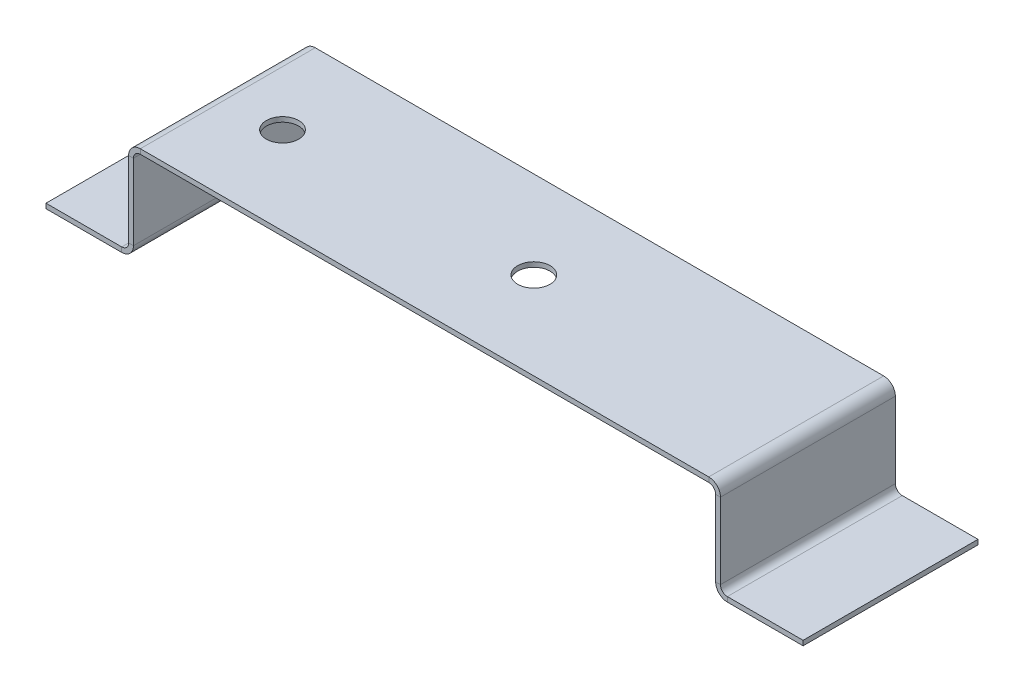
SolidWorks part; units mm, degrees
note: The reader was unsure of these and kept them because the rebuilt part matched: flange length of "Edge-Flange1", "Edge-Flange2", "Edge-Flange3", "Edge-Flange4".
ref_plane "Front Plane" through (0, 0, 0) normal (0, 0, 1) x (1, 0, 0)
ref_plane "Top Plane" through (0, 0, 0) normal (0, 1, 0) x (1, 0, 0)
ref_plane "Right Plane" through (0, 0, 0) normal (1, 0, 0) x (0, 0, -1)
sketch "Sketch1" plane through (0, 0, 0) normal (0, 1, 0) x (1, 0, 0)
  line L1 (-41.275, -12.7) -> (41.275, -12.7)
  line L2 (-41.275, -12.7) -> (-41.275, 12.7)
  line L3 (-41.275, 12.7) -> (41.275, 12.7)
  line L4 (41.275, -12.7) -> (41.275, 12.7)
  line L5 (-41.275, -12.7) -> (41.275, 12.7) construction
  line L6 (-41.275, 12.7) -> (41.275, -12.7) construction
  point P0 (0, 0)
  dimension "D1" = 25.4
  dimension "D2" = 82.55
base flange "Base-Flange1" sketch "Sketch1" thickness 0.7 reverse thickness direction no parameters "D1"=1
edge flange "Edge-Flange1" sketch "Sketch8" flange angle 90 flange length 12.7 flange position bend outside bend radius 1 thickness 0.7 relief rectangular parameters "D6"=0
sketch "Sketch8" plane through (41.275, -0.7, 0) normal (-1, 0, 0) x (0, 0, -1)
  line L2 (-12.7, 0) -> (-12.7, 12)
  line L3 (-12.7, 12) -> (12.7, 12)
  line L4 (12.7, 12) -> (12.7, 0)
  line L6 (12.7, 0) -> (-12.7, 0) construction
  line L7 (12.7, 0) -> (-12.7, 0)
bend "EdgeBend1" bend radius 1 bend angle 90 parameters "D5"=1
edge flange "Edge-Flange2" sketch "Sketch11" flange angle 90 flange length 12.7 flange position bend outside bend radius 1 thickness 0.7 relief rectangular parameters "D6"=0
sketch "Sketch11" plane through (42.975, -12.7, 0) normal (0, -1, 0) x (0, 0, -1)
  line L0 (12.7, 0) -> (-12.7, 0) construction
  line L1 (12.7, 0) -> (-12.7, 0)
  line L2 (-12.7, 0) -> (-12.7, 12)
  line L3 (-12.7, 12) -> (12.7, 12)
  line L4 (12.7, 12) -> (12.7, 0)
bend "EdgeBend2" bend radius 1 bend angle 90 parameters "D5"=2
edge flange "Edge-Flange3" sketch "Sketch15" flange angle 90 flange length 12.7 flange position bend outside bend radius 1 thickness 0.7 relief rectangular parameters "D6"=0
sketch "Sketch15" plane through (-41.275, -0.7, 0) normal (1, 0, 0) x (0, 0, 1)
  line L1 (12.7, 0) -> (-12.7, 0) construction
  line L2 (-12.7, 0) -> (-12.7, 12)
  line L3 (-12.7, 12) -> (12.7, 12)
  line L4 (12.7, 12) -> (12.7, 0)
  line L5 (12.7, 0) -> (-12.7, 0)
bend "EdgeBend3" bend radius 1 bend angle 90 parameters "D5"=3
edge flange "Edge-Flange4" sketch "Sketch18" flange angle 90 flange length 12.7 flange position bend outside bend radius 1 thickness 0.7 relief rectangular parameters "D6"=0
sketch "Sketch18" plane through (-42.975, -12.7, 0) normal (0, 1, 0) x (0, 0, -1)
  line L1 (12.7, 0) -> (-12.7, 0) construction
  line L2 (-12.7, 0) -> (-12.7, 12)
  line L3 (-12.7, 12) -> (12.7, 12)
  line L4 (12.7, 12) -> (12.7, 0)
  line L5 (12.7, 0) -> (-12.7, 0)
bend "EdgeBend4" bend radius 1 bend angle 90 parameters "D5"=4
sketch "Sketch19" plane through (0, 0, 0) normal (0, 1, 0) x (1, 0, 0)
  line L0 (41.275, 12.7) -> (-41.275, 12.7) construction
  line L1 (-41.275, 12.7) -> (-41.275, -12.7) construction
  line L2 (41.275, -12.7) -> (41.275, 12.7) construction
  circle A0 centre (-33.3248, 0) radius 2.35
  circle A1 centre (3.175, 0) radius 2.35
  dimension "D1" = 12.7
  dimension "D2" = 7.9502
  dimension "D3" = 12.7
  dimension "D4" = 38.1
  dimension "D5" = 36.4998
extrude "Cut-Extrude1" cut sketch "Sketch19" against normal through all normal cut yes
sketch "Bend-Lines1" [suppressed] plane through (0, 0, 0) normal (0, 1, 0) x (1, 0, 0)
sketch "Bounding-Box1" [suppressed] plane through (0, 0, 0) normal (0, 1, 0) x (1, 0, 0)
sheet metal parameters "Sheet-Metal1" thickness 0.7 parameters "D1"=1
flat pattern "Flat-Pattern1" [suppressed]
sketch "Bend-Lines2" plane through (0, 0, 0) normal (0, 1, 0) x (1, 0, 0)
sketch "Bounding-Box2" [suppressed] plane through (0, 0, 0) normal (0, 1, 0) x (1, 0, 0)
sheet metal parameters "Sheet-Metal2" thickness 0.7 parameters "D1"=1
flat pattern "Flat-Pattern1" [suppressed]
sketch "Bend-Lines2" plane through (0, 0, 0) normal (0, 1, 0) x (1, 0, 0)
sketch "Bounding-Box2" [suppressed] plane through (0, 0, 0) normal (0, 1, 0) x (1, 0, 0)
bend of the flat pattern "Flatten-<EdgeBend1>1"
sheet metal parameters "Sheet-Metal3" thickness 0.7 parameters "D1"=1
flat pattern "Flat-Pattern1" [suppressed]
sketch "Bend-Lines2" plane through (0, 0, 0) normal (0, 1, 0) x (1, 0, 0)
  line L0 (55.4559, -12.7) -> (55.4559, 12.7) construction
  line L1 (42.3353, -12.7) -> (42.3353, 12.7) construction
  line L2 (55.4559, -12.7) -> (55.4559, 12.7) construction
  line L3 (42.3353, -12.7) -> (42.3353, 12.7) construction
sketch3d "Bounding-Box2" [suppressed]
  line L0 (67.5162, 12.7, 0) -> (-41.275, 12.7, 0) construction
  line L1 (67.5162, -12.7, 0) -> (-41.275, -12.7, 0) construction
  line L2 (67.5162, 12.7, 0) -> (67.5162, -12.7, 0) construction
  line L3 (-41.275, 12.7, 0) -> (-41.275, -12.7, 0) construction
bend of the flat pattern "Flatten-<EdgeBend1>1"
bend of the flat pattern "Flatten-<EdgeBend2>1"
sheet metal parameters "Sheet-Metal4" thickness 0.7 parameters "D1"=1
flat pattern "Flat-Pattern1" [suppressed]
sketch "Bend-Lines2" plane through (0, 0, 0) normal (0, 1, 0) x (1, 0, 0)
  line L0 (55.4559, -12.7) -> (55.4559, 12.7) construction
  line L1 (42.3353, -12.7) -> (42.3353, 12.7) construction
  line L2 (55.4559, -12.7) -> (55.4559, 12.7) construction
  line L3 (42.3353, -12.7) -> (42.3353, 12.7) construction
sketch3d "Bounding-Box2" [suppressed]
  line L0 (67.5162, 12.7, 0) -> (-41.275, 12.7, 0) construction
  line L1 (67.5162, -12.7, 0) -> (-41.275, -12.7, 0) construction
  line L2 (67.5162, 12.7, 0) -> (67.5162, -12.7, 0) construction
  line L3 (-41.275, 12.7, 0) -> (-41.275, -12.7, 0) construction
bend of the flat pattern "Flatten-<EdgeBend1>1"
bend of the flat pattern "Flatten-<EdgeBend3>1"
bend of the flat pattern "Flatten-<EdgeBend2>1"
sheet metal parameters "Sheet-Metal5" thickness 0.7 parameters "D1"=1
flat pattern "Flat-Pattern1" [suppressed]
sketch "Bend-Lines2" plane through (0, 0, 0) normal (0, 1, 0) x (1, 0, 0)
  line L0 (55.4559, -12.7) -> (55.4559, 12.7) construction
  line L1 (42.3353, -12.7) -> (42.3353, 12.7) construction
  line L2 (55.4559, -12.7) -> (55.4559, 12.7) construction
  line L3 (42.3353, -12.7) -> (42.3353, 12.7) construction
sketch3d "Bounding-Box2" [suppressed]
  line L0 (67.5162, 12.7, 0) -> (-41.275, 12.7, 0) construction
  line L1 (67.5162, -12.7, 0) -> (-41.275, -12.7, 0) construction
  line L2 (67.5162, 12.7, 0) -> (67.5162, -12.7, 0) construction
  line L3 (-41.275, 12.7, 0) -> (-41.275, -12.7, 0) construction
bend of the flat pattern "Flatten-<EdgeBend1>1"
bend of the flat pattern "Flatten-<EdgeBend3>1"
bend of the flat pattern "Flatten-<EdgeBend4>1"
bend of the flat pattern "Flatten-<EdgeBend2>1"
sheet metal parameters "Sheet-Metal6" thickness 0.7 parameters "D1"=1
flat pattern "Flat-Pattern1"
sketch "Bend-Lines2" plane through (0, 0, 0) normal (0, 1, 0) x (1, 0, 0)
  line L0 (55.4559, -12.7) -> (55.4559, 12.7) construction
  line L1 (42.3353, -12.7) -> (42.3353, 12.7) construction
  line L2 (55.4559, -12.7) -> (55.4559, 12.7) construction
  line L3 (42.3353, -12.7) -> (42.3353, 12.7) construction
  line L4 (-55.4559, 12.7) -> (-55.4559, -12.7) construction
  line L5 (-42.3353, 12.7) -> (-42.3353, -12.7) construction
  line L6 (-55.4559, 12.7) -> (-55.4559, -12.7) construction
  line L7 (-42.3353, 12.7) -> (-42.3353, -12.7) construction
sketch3d "Bounding-Box2" [suppressed]
  line L0 (67.5162, 12.7, 0) -> (-67.5162, 12.7, 0) construction
  line L1 (67.5162, -12.7, 0) -> (-67.5162, -12.7, 0) construction
  line L2 (67.5162, 12.7, 0) -> (67.5162, -12.7, 0) construction
  line L3 (-67.5162, 12.7, 0) -> (-67.5162, -12.7, 0) construction
bend of the flat pattern "Flatten-<EdgeBend1>1"
bend of the flat pattern "Flatten-<EdgeBend3>1"
bend of the flat pattern "Flatten-<EdgeBend4>1"
bend of the flat pattern "Flatten-<EdgeBend2>1"
